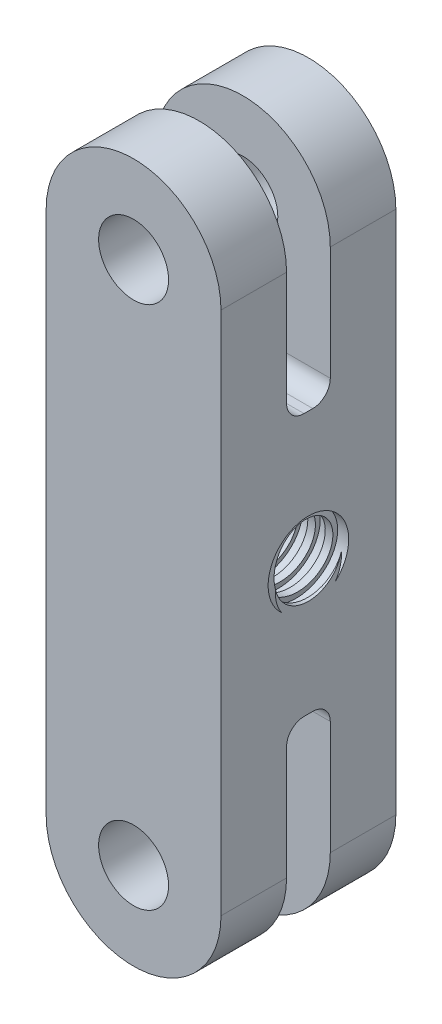
SolidWorks part; units mm, degrees
ref_plane "Front Plane" through (0, 0, 0) normal (0, 0, 1) x (1, 0, 0)
ref_plane "Top Plane" through (0, 0, 0) normal (0, 1, 0) x (1, 0, 0)
ref_plane "Right Plane" through (0, 0, 0) normal (1, 0, 0) x (0, 0, -1)
sketch "Sketch1" plane through (0, 0, 0) normal (0, 0, 1) x (1, 0, 0)
  line L0 (-10, 60) -> (-10, 0)
  line L2 (10, 0) -> (10, 60)
  circle A0 centre (0, 0) radius 4
  circle A1 centre (0, 60) radius 4
  arc A2 (10, 60) -> (-10, 60) centre (0, 60) ccw
  arc A3 (-10, 0) -> (10, 0) centre (0, 0) ccw
  dimension "D1" = 8
  dimension "D2" = 8
  dimension "D4" = 20
  dimension "D5" = 20
  dimension "D3" = 60
extrude "Boss-Extrude1" add sketch "Sketch1" against normal blind 20
sketch "Sketch2" plane through (-10, 0, 0) normal (-1, 0, 0) x (0, 0, 1)
  line L0 (-20, 0) -> (-20, -10) construction
  line L1 (0, 70) -> (-20, 70) construction
  line L2 (-20, 70) -> (-20, 60) construction
  line L3 (-12.5, 75) -> (-7.5, 75)
  line L4 (-12.5, 75) -> (-12.5, 45)
  line L5 (-12.5, 45) -> (-7.5, 45)
  line L6 (-7.5, 75) -> (-7.5, 45)
  line L7 (-10, 30) -> (1.7861, 30) construction
  line L8 (-12.5, -15) -> (-7.5, -15)
  line L9 (-12.5, 15) -> (-7.5, 15)
  line L10 (-12.5, -15) -> (-12.5, 15)
  line L11 (-7.5, -15) -> (-7.5, 15)
  circle A0 centre (-10, 30) radius 3.85
  dimension "D3" = 7.7
  dimension "D1" = 10
  dimension "D2" = 40
  dimension "D4" = 5
  dimension "D5" = 7.5
  dimension "D6" = 15
  dimension "D7" = 30
extrude "Cut-Extrude1" cut sketch "Sketch2" against normal through all
fillet "Fillet1" radius 2 4 edges at (0, 15, -7.5) (0, 15, -12.5) (0, 45, -12.5) (0, 45, -7.5)
ref_plane "Plane3" through (14.75, 0, 0) normal (1, 0, 0) x (0, 0, -1)
sketch "Sketch4" plane through (14.75, 0, 0) normal (1, 0, 0) x (0, 0, -1)
  circle A0 centre (10, 30) radius 4
curve "Helix/Spiral1" pitch 2 height 40 turns 20
ref_plane "Plane2" through (0, 0, -10) normal (0, 0, 1) x (1, 0, 0)
sketch "Sketch9" plane through (0, 0, -10) normal (0, 0, 1) x (1, 0, 0)
  line L0 (10.7679, 34.6057) -> (9.5, 33.6057) construction
  line L1 (9.5, 33.6057) -> (9.2321, 34.6057)
  line L2 (9.2321, 34.6057) -> (10.4942, 33.6102) construction
  line L3 (10, 0) -> (10, 60) construction
  line L4 (10.7679, 34.6057) -> (10.5, 33.6057)
  line L5 (10.5, 33.6057) -> (9.5, 33.6057)
  line L6 (9.2321, 34.6057) -> (10.7679, 34.6057)
  point P6 (10, 33.6057)
  point P11 (10, 34)
  dimension "D1" = 1
  dimension "D2" = 1
  dimension "D3" = 105
  dimension "D4" = 30
  dimension "D5" = 0
  dimension "D6" = 34
  dimension "D7" = 10
sweep "Cut-Sweep1" cut profiles "Sketch9" path "Helix/Spiral1"
